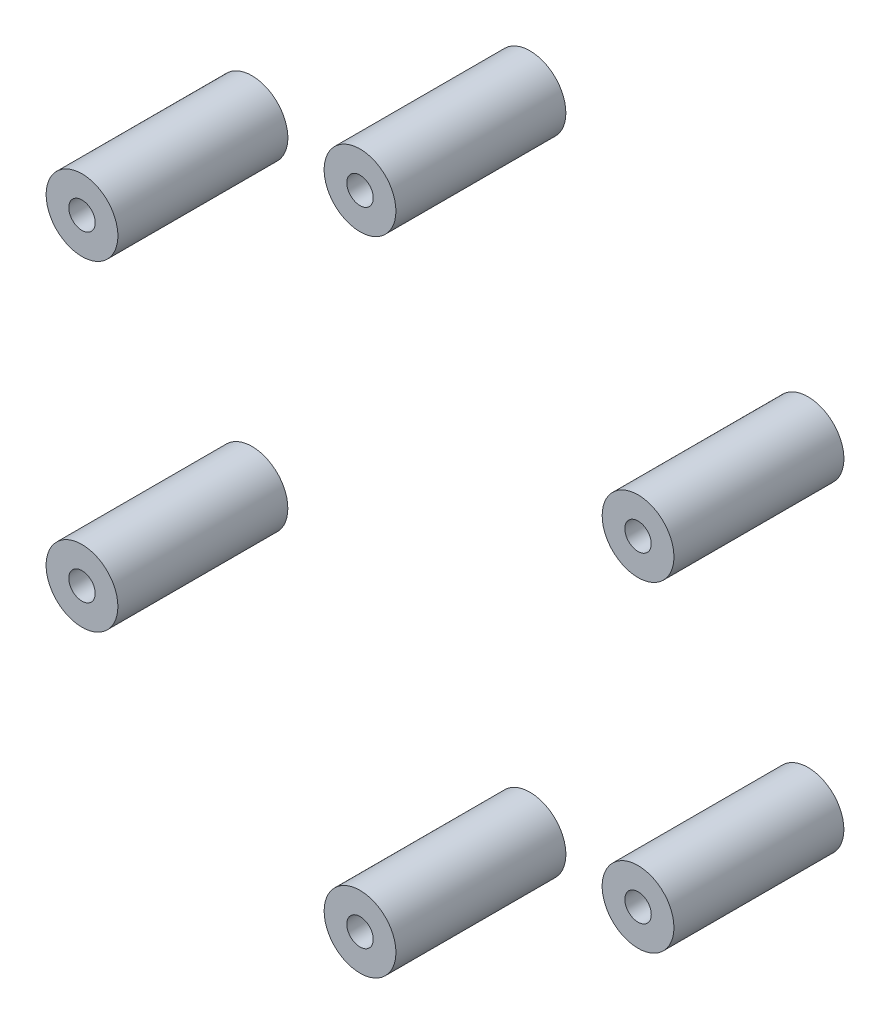
SolidWorks part; units mm, degrees
material "Nylon 101"
ref_plane "Front Plane" through (0, 0, 0) normal (0, 0, 1) x (1, 0, 0)
ref_plane "Top Plane" through (0, 0, 0) normal (0, 1, 0) x (1, 0, 0)
ref_plane "Right Plane" through (0, 0, 0) normal (1, 0, 0) x (0, 0, -1)
sketch "Sketch2" plane through (0, 0, 0) normal (0, 0, 1) x (0, 1, 0)
  circle A0 centre (34, 0) radius 1.8
sketch "Screw Hole" plane through (0, 0, 0) normal (0, 0, 1) x (1, 0, 0)
  circle A0 centre (0, 34) radius 1.4
  circle A1 centre (0, 34) radius 3.8
  point P0 (0, 0)
  dimension "D1" = 2.8
  dimension "D2" = 7.6
ref_axis "Axis1" through (0, 0, 0) along (0, 0, 1)
extrude "Boss-Extrude1" add sketch "Screw Hole" along normal mid plane 18
pattern_circular "CirPattern1" count 6 over 360 about axis through (0, 0, 0) along (0, 0, 1) of bodies 102
